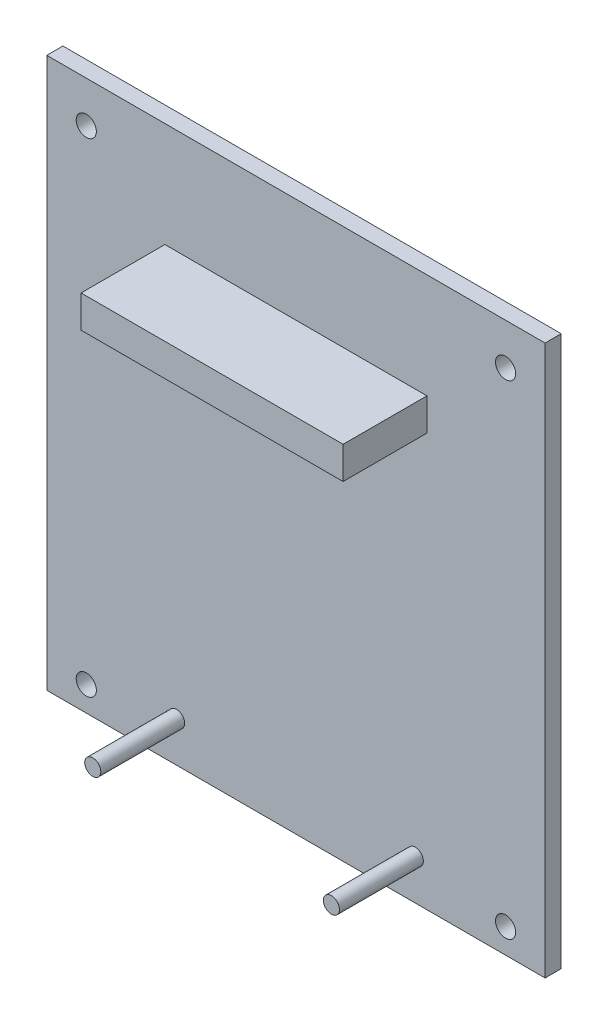
SolidWorks part; units mm, degrees
ref_plane "Front Plane" through (0, 0, 0) normal (0, 0, 1) x (1, 0, 0)
ref_plane "Top Plane" through (0, 0, 0) normal (0, 1, 0) x (1, 0, 0)
ref_plane "Right Plane" through (0, 0, 0) normal (1, 0, 0) x (0, 0, -1)
sketch "Sketch1" plane through (0, 0, 0) normal (0, 0, 1) x (1, 0, 0)
  line L0 (6.223, 80.1116) -> (72.263, 80.1116) construction
  line L1 (0, 86.614) -> (78.486, 86.614)
  line L2 (0, 86.614) -> (0, 0)
  line L3 (0, 0) -> (78.486, 0)
  line L4 (78.486, 86.614) -> (78.486, 0)
  line L5 (72.263, 80.1116) -> (72.263, 3.9116) construction
  line L6 (72.263, 3.9116) -> (6.223, 3.9116) construction
  line L7 (6.223, 3.9116) -> (6.223, 80.1116) construction
  line L8 (39.243, 86.614) -> (39.243, 0) construction
  line L9 (6.223, 42.0116) -> (72.263, 42.0116) construction
  circle A0 centre (6.223, 80.1116) radius 1.5875
  circle A1 centre (72.263, 80.1116) radius 1.5875
  circle A2 centre (72.263, 3.9116) radius 1.5875
  circle A3 centre (6.223, 3.9116) radius 1.5875
  point P18 (39.243, 42.0116)
  point P22 (39.243, 43.307)
  dimension "D3" = 3.175
  dimension "D1" = 76.2
  dimension "D2" = 66.04
  dimension "D4" = 78.486
  dimension "D5" = 86.614
  dimension "D6" = 2.5908
extrude "Boss-Extrude1" add sketch "Sketch1" along normal blind 2.54
sketch "Sketch2" plane through (0, 0, 2.54) normal (0, 0, 1) x (1, 0, 0)
  line L0 (39.243, 86.614) -> (39.243, 70.104) construction
  line L1 (18.6055, 70.104) -> (59.8805, 70.104)
  line L2 (18.6055, 70.104) -> (18.6055, 65.024)
  line L3 (18.6055, 65.024) -> (59.8805, 65.024)
  line L4 (59.8805, 70.104) -> (59.8805, 65.024)
  line L5 (78.486, 86.614) -> (0, 86.614) construction
  line L6 (20.447, 6.35) -> (58.039, 6.35) construction
  line L7 (39.243, 6.35) -> (39.243, 0) construction
  line L8 (0, 0) -> (78.486, 0) construction
  circle A0 centre (20.447, 6.35) radius 1.27
  circle A1 centre (58.039, 6.35) radius 1.27
  dimension "D6" = 2.54
  dimension "D1" = 5.08
  dimension "D2" = 41.275
  dimension "D3" = 16.51
  dimension "D4" = 6.35
  dimension "D5" = 37.592
extrude "Boss-Extrude2" add sketch "Sketch2" along normal blind 13.208
